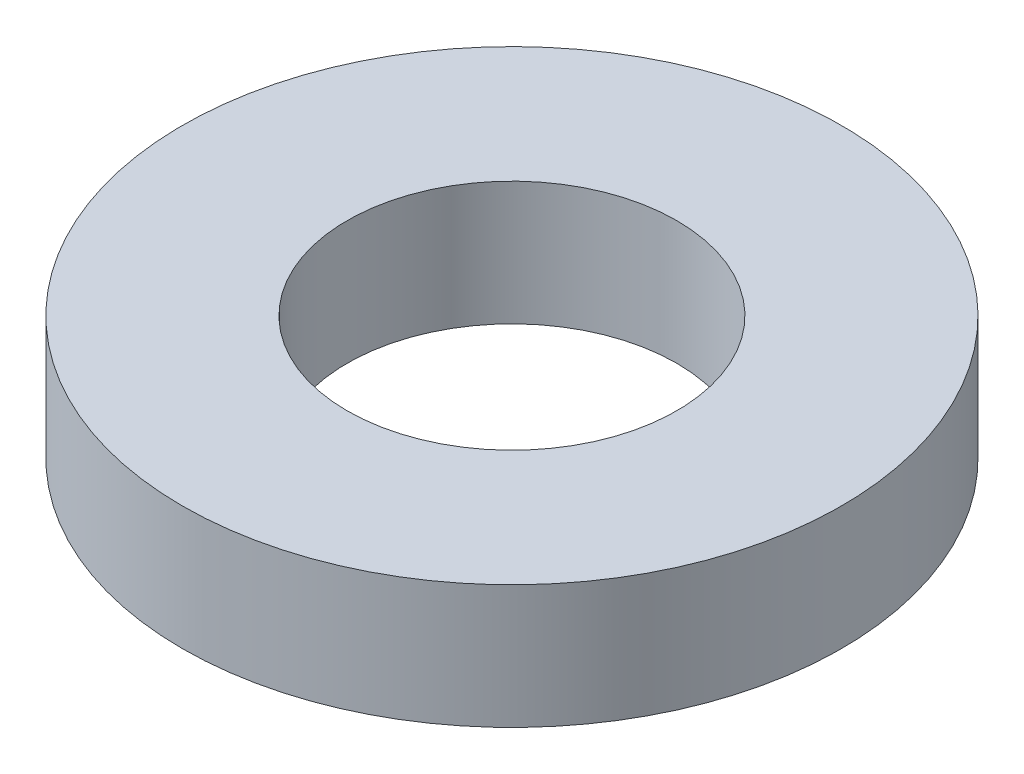
SolidWorks part; units mm, degrees
ref_plane "Front Plane" through (0, 0, 0) normal (0, 0, 1) x (1, 0, 0)
ref_plane "Top Plane" through (0, 0, 0) normal (0, 1, 0) x (1, 0, 0)
ref_plane "Right Plane" through (0, 0, 0) normal (1, 0, 0) x (0, 0, -1)
sketch "Sketch1" plane through (0, 0, 0) normal (0, 1, 0) x (1, 0, 0)
  circle A0 centre (0, 0) radius 40
  dimension "FLANGE_OD" = 80
extrude "Boss-Extrude1" add sketch "Sketch1" along normal blind 15
sketch "Sketch2" plane through (0, 0, 0) normal (0, 1, 0) x (1, 0, 0)
  circle A0 centre (0, 0) radius 20
  dimension "BORE_D" = 40
extrude "Cut-Extrude1" cut sketch "Sketch2" along normal through all
sketch "Sketch3" plane through (0, 15, 0) normal (0, 1, 0) x (1, 0, 0)
  circle A0 centre (0, 0) radius 17.7031 construction
  circle A1 centre (-17.7031, 0) radius 2.0883
  dimension "BOLT_D" = 4.1767
  dimension "BOLT_PCD" = 35.4062
extrude "Cut-Extrude2" cut sketch "Sketch3" against normal blind 9.6563 rebuild error yes
pattern_circular "CirPattern1" count 5 over 360 rebuild error yes
